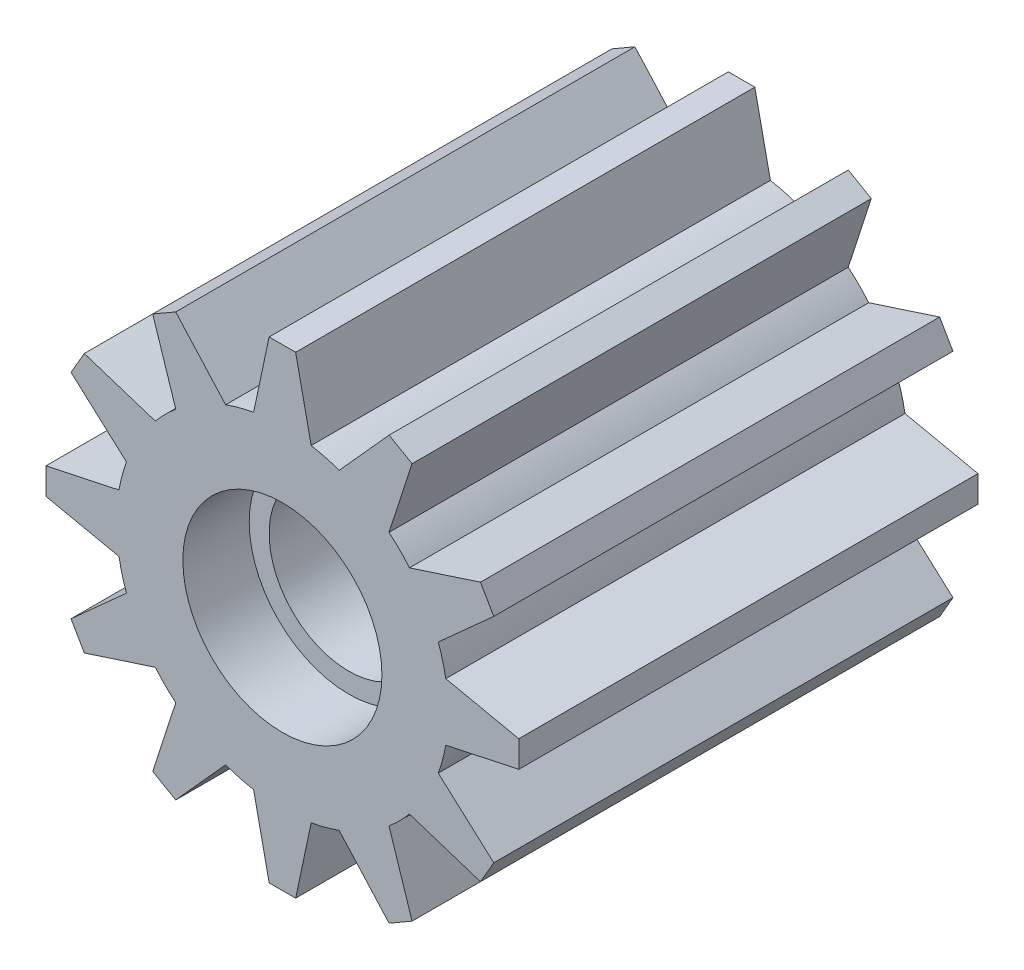
SolidWorks part; units mm, degrees
ref_plane "Plan de face" through (0, 0, 0) normal (0, 0, 1) x (1, 0, 0)
ref_plane "Plan de dessus" through (0, 0, 0) normal (0, 1, 0) x (1, 0, 0)
ref_plane "Plan de droite" through (0, 0, 0) normal (1, 0, 0) x (0, 0, -1)
sketch "Esquisse1" plane through (0, 0, 0) normal (0, 0, 1) x (1, 0, 0)
  circle A0 centre (0, 0) radius 12.5
  dimension "D1" = 25
extrude "Boss.-Extru.1" add sketch "Esquisse1" along normal blind 34.6
sketch "Esquisse3" plane through (0, 0, 34.6) normal (0, 0, 1) x (1, 0, 0)
  line L0 (0, 60.9582) -> (0, -63.5723) construction
  line L5 (-2.1691, 12.3104) -> (-1, 17.8104)
  line L6 (1, 17.8104) -> (-1, 17.8104)
  line L7 (-2.1691, 12.3104) -> (0, 0) construction
  line L8 (2.1691, 12.3104) -> (1, 17.8104)
  line L9 (2.1691, 12.3104) -> (-3.4751, 12.3104) construction
  circle A4 centre (0, 0) radius 12.5 construction
  circle A5 centre (0, 0) radius 12.5
  point P8 (0, 17.8104)
  circle M11 centre (0, 0) radius 12.5
  dimension "D2" = 1
  dimension "D1" = 5.5
  dimension "D3" = 102
extrude "Boss.-Extru.2" add sketch "Esquisse3" against normal blind 34.6 contours L8 L6 L5 M11 region at (0, 14.7982, 34.6)
ref_axis "Axe1" through (0, 0, 34.6) along (0, 0, -1)
pattern_circular "Répétition circulaire1" count 12 over 360 about axis through (0, 0, 34.6) along (0, 0, -1) of "Boss.-Extru.2"
sketch "Esquisse5" plane through (0, 0, 34.6) normal (0, 0, 1) x (1, 0, 0)
  circle A0 centre (0, 0) radius 7.5
  dimension "D1" = 15
extrude "Enlèv. mat.-Extru.2" cut sketch "Esquisse5" against normal blind 5
sketch "Esquisse6" plane through (0, 0, 29.6) normal (0, 0, 1) x (1, 0, 0)
  circle A0 centre (0, 0) radius 6
  dimension "D1" = 12
extrude "Enlèv. mat.-Extru.3" cut sketch "Esquisse6" against normal blind 24.6
sketch "Esquisse7" plane through (0, 0, 0) normal (0, 0, -1) x (-1, 0, 0)
  circle A0 centre (0, 0) radius 7.5
  dimension "D1" = 15
extrude "Enlèv. mat.-Extru.4" cut sketch "Esquisse7" against normal blind 5
equation "\"gearEpis\"= 34.6"
equation "\"roulEpis\"= 5"
equation "\"roulD\"= 15"
equation "\"D1@Esquisse5\"=\"roulD\""
equation "\"D1@Enlèv. mat.-Extru.2\"=\"roulEpis\""
equation "\"D1@Enlèv. mat.-Extru.3\"=\"gearEpis\"-\"roulEpis\"*2"
equation "\"D1@Esquisse7\"=\"roulD\""
equation "\"D1@Enlèv. mat.-Extru.4\"=\"roulEpis\""
equation "\"holeD\" = 12"
equation "\"D1@Esquisse6\"=\"holeD\""
